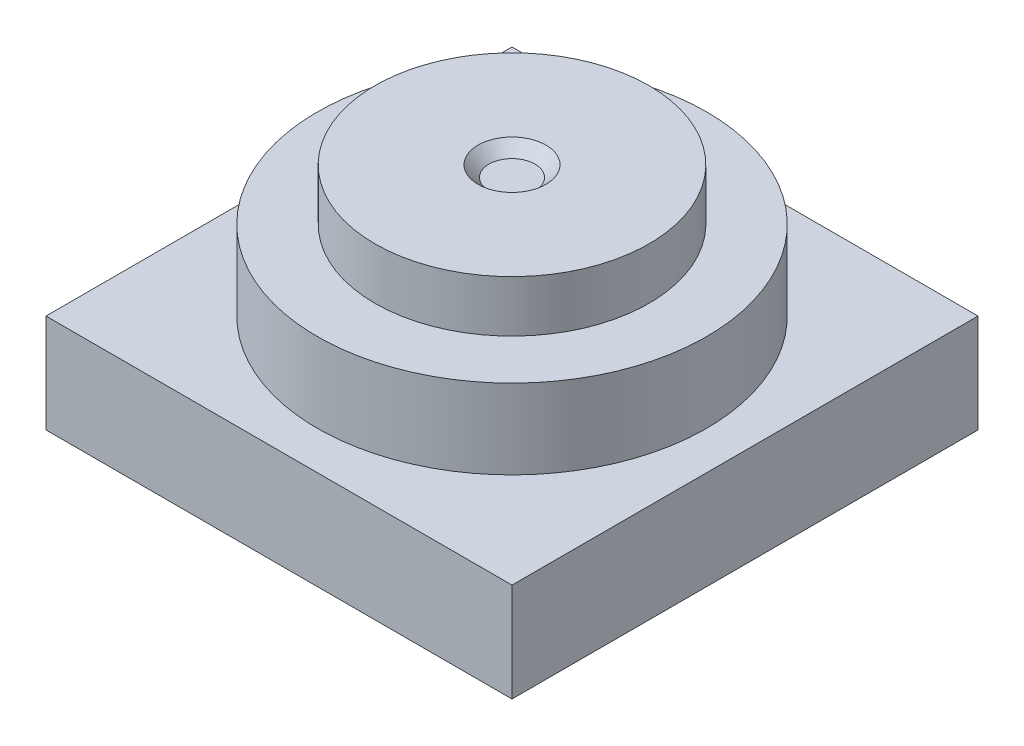
SolidWorks part; units mm, degrees
ref_plane "前视基准面" through (0, 0, 0) normal (0, 0, 1) x (1, 0, 0)
ref_plane "上视基准面" through (0, 0, 0) normal (0, 1, 0) x (1, 0, 0)
ref_plane "右视基准面" through (0, 0, 0) normal (1, 0, 0) x (0, 0, -1)
sketch "草图1" plane through (0, 0, 0) normal (0, 1, 0) x (1, 0, 0)
  line L1 (-4.25, 4.25) -> (4.25, 4.25)
  line L2 (-4.25, 4.25) -> (-4.25, -4.25)
  line L3 (-4.25, -4.25) -> (4.25, -4.25)
  line L4 (4.25, 4.25) -> (4.25, -4.25)
  line L5 (-4.25, 4.25) -> (4.25, -4.25) construction
  line L6 (-4.25, -4.25) -> (4.25, 4.25) construction
  circle A0 centre (0, 0) radius 3.55
  circle A1 centre (0, 0) radius 2.5
  point P0 (0, 0)
  point P8 (0, 0)
  dimension "D2" = 7.1
  dimension "D3" = 5
  dimension "D1" = 8.5
extrude "凸台-拉伸2" add sketch "草图1" along normal blind 1.8 contours L4 L1 L2 L3 A0 region at (0, 0, -4.1298)
extrude "凸台-拉伸3" add sketch "草图1<3>" along normal blind 3.25 contours A0 A1 region at (-3.4496, 0, 0)
sketch "草图1<3>" plane through (0, 0, 0) normal (0, 1, 0) x (1, 0, 0) same geometry as "草图1"
extrude "凸台-拉伸4" add sketch "草图1<4>" along normal blind 4.19 contours A1 region at (0, 0, 0)
sketch "草图1<4>" plane through (0, 0, 0) normal (0, 1, 0) x (1, 0, 0) same geometry as "草图1"
sketch "草图3" plane through (0, 4.19, 0) normal (0, 1, 0) x (1, 0, 0)
  circle A0 centre (0, 0) radius 0.42
  dimension "D1" = 0.84
extrude "切除-拉伸1" cut sketch "草图3" against normal blind 0.2
chamfer "倒角1" distance 0.2 angle 45 1 edges at (0, 4.19, 0.42)
